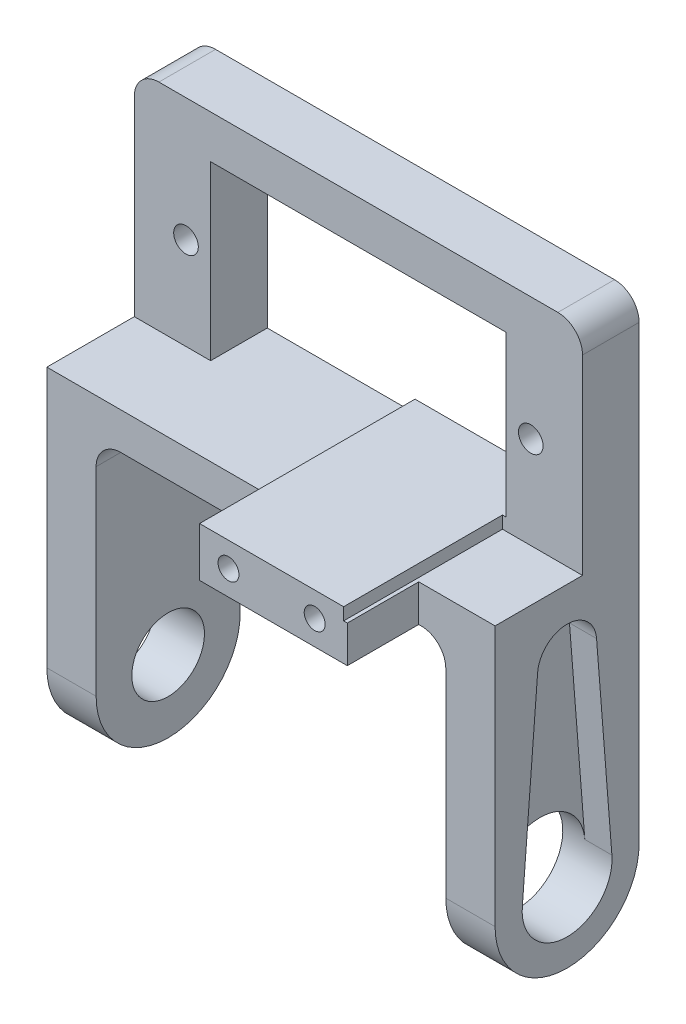
SolidWorks part; units mm, degrees
note: The reader was unsure of these and kept them because the rebuilt part matched: shared geometry of "草图1<3>", "草图1<4>", "草图2<3>", "草图1<6>", "草图4<3>", "草图2<4>", "草图2<5>".
ref_plane "前视基准面" through (0, 0, 0) normal (0, 0, 1) x (1, 0, 0)
ref_plane "上视基准面" through (0, 0, 0) normal (0, 1, 0) x (1, 0, 0)
ref_plane "右视基准面" through (0, 0, 0) normal (1, 0, 0) x (0, 0, -1)
sketch "草图1" plane through (0, 0, 0) normal (0, 0, 1) x (1, 0, 0)
  line L0 (0, 0) -> (0, 44.5)
  line L1 (0, 44.5) -> (36.4, 44.5)
  line L2 (36.4, 44.5) -> (36.4, 0)
  line L3 (36.4, 0) -> (32.4, 0)
  line L4 (32.4, 0) -> (32.4, 24)
  line L5 (32.4, 24) -> (4, 24)
  line L6 (4, 24) -> (4, 0)
  line L7 (4, 0) -> (0, 0)
  line L8 (6.2, 41) -> (6.2, 28)
  line L9 (6.2, 28) -> (30.2, 28)
  line L10 (30.2, 28) -> (30.2, 41)
  line L11 (30.2, 41) -> (6.2, 41)
  line L12 (18.2, 37.1433) -> (18.2, 17.0175) construction
  line L13 (5.5, 34.5) -> (29.5, 34.5) construction
  line L14 (18.2, 28) -> (18.2, 27)
  line L15 (0, 27) -> (35, 27) construction
  line L16 (6.5, 27) -> (6.5, 28) construction
  line L17 (6.5, 27) -> (0, 27) construction
  line L18 (6.5, 27) -> (18.2, 27) construction
  line L19 (12.35, 27) -> (12.35, 38.1786) construction
  line L20 (6.2, 28) -> (6.2, 24)
  line L21 (6.6587, 26) -> (12.3538, 26) construction
  line L22 (18.2, 28) -> (18.2, 24)
  line L23 (29.9, 27) -> (29.9, 28)
  line L24 (29.9, 27) -> (36.4, 27)
  line L25 (30.2, 27) -> (30.2, 24)
  line L26 (0, 27) -> (6.2, 27)
  line L27 (6.2, 27) -> (6.2, 28)
  line L28 (6.2, 27) -> (18.2, 27)
  circle A0 centre (32.2, 34.5) radius 1
  circle A1 centre (4.2, 34.5) radius 1
  circle A2 centre (15.85, 26) radius 0.85 construction
  circle A3 centre (8.85, 26) radius 0.85 construction
  circle A4 centre (27.55, 26) radius 0.85
  circle A5 centre (20.55, 26) radius 0.85
  point P16 (6.2, 34.5)
  point P28 (18.2, 26)
  dimension "D8" = 2
  dimension "D13" = 1.7
  dimension "D1" = 36.4
  dimension "D2" = 4
  dimension "D3" = 24
  dimension "D4" = 13
  dimension "D5" = 3.5
  dimension "D6" = 4
  dimension "D7" = 24
  dimension "D9" = 2
  dimension "D10" = 1
  dimension "D12" = 11.7
  dimension "D14" = 7
extrude "凸台-拉伸1" add sketch "草图1" along normal blind 4.6 contours L20 L8 L11 L10 L9 L14 L15 L2 L1 L0 L17 A1 A0
extrude "凸台-拉伸2" add sketch "草图1<3>" along normal blind 11.7 contours L15 L22 L5 L4 L3 L2 | L20 L17 L0 L7 L6 L5
sketch "草图1<3>" plane through (0, 0, 0) normal (0, 0, 1) x (1, 0, 0) same geometry as "草图1"
extrude "凸台-拉伸3" add sketch "草图1<4>" along normal blind 11.7 contours L22 L14 L9 L16 L17 L20 L5 A3 A2
sketch "草图1<4>" plane through (0, 0, 0) normal (0, 0, 1) x (1, 0, 0) same geometry as "草图1"
sketch "草图2" plane through (0, 0, 0) normal (-1, 0, 0) x (0, 0, 1)
  line L0 (0, 5.85) -> (13.9097, 5.85) construction
  line L1 (8.2426, 21.9881) -> (9.4888, 6.1361)
  line L2 (11.7, 0) -> (0, 0) construction
  line L3 (5.85, 0) -> (5.85, 14.3706) construction
  line L4 (3.4574, 21.9881) -> (2.2112, 6.1361)
  line L5 (11.7, 0) -> (0, 0)
  circle A0 centre (5.85, 5.85) radius 3.65
  arc A1 (8.2426, 21.9881) -> (3.4574, 21.9881) centre (5.85, 21.8) ccw
  point P5 (5.85, 7.1853)
  point P9 (5.85, 0)
  point P16 (5.85, 24.2)
  point P17 (5.85, 2.2)
  dimension "D2" = 7.3
  dimension "D3" = 4.8
  dimension "D1" = 5.85
  dimension "D4" = 22
extrude "切除-拉伸1" cut sketch "草图2" against normal blind 24.5 contours A0
extrude "切除-拉伸2" cut sketch "草图2<3>" against normal blind 2.2 contours L1 A1 L4 A0
sketch "草图2<3>" plane through (0, 0, 0) normal (-1, 0, 0) x (0, 0, 1) same geometry as "草图2"
fillet "圆角2" radius 5.85 1 edges at (2, 0, 0)
fillet "圆角3" radius 5.85 1 edges at (34.4, 0, 0)
fillet "圆角4" radius 5.85 3 edges at (34.4, 0, 11.7) (32.4, 0, 8.775) (36.4, 0, 8.775)
fillet "圆角1" radius 5.85 3 edges at (2, 0, 11.7) (0, 0, 8.775) (4, 0, 8.775)
fillet "圆角5" radius 2 1 edges at (0, 44.5, 2.3)
fillet "圆角6" radius 2 1 edges at (36.4, 44.5, 2.3)
fillet "圆角8" radius 2 1 edges at (4, 24, 5.85)
sketch "草图3" plane through (36.4, 0, 0) normal (1, 0, 0) x (0, 0, -1)
  line L3 (0, 5.85) -> (0, 22)
  line L4 (0, 22) -> (-11.7, 22)
  line L5 (-11.7, 22) -> (-11.7, 5.85)
  line L6 (0, 5.85) -> (0, 22)
  line L7 (0, 22) -> (-11.7, 22)
  line L8 (-11.7, 22) -> (-11.7, 5.85)
  circle A0 centre (-5.85, 5.85) radius 2.95
  arc A2 (-11.7, 5.85) -> (-5.85, 0) centre (-5.85, 5.85) ccw
  arc A3 (-5.85, 0) -> (0, 5.85) centre (-5.85, 5.85) ccw
  arc A4 (-11.7, 5.85) -> (-5.85, 0) centre (-5.85, 5.85) ccw
  arc A5 (-5.85, 0) -> (0, 5.85) centre (-5.85, 5.85) ccw
  dimension "D2" = 5.9
  dimension "D1" = 0
extrude "切除-拉伸3" cut sketch "草图3" against normal blind 10 contours A0
extrude "凸台-拉伸5" add sketch "草图1<6>" along normal blind 17.5 contours L25 L24 L23 L9 L14 L22 L5 A4 A5
sketch "草图1<6>" plane through (0, 0, 0) normal (0, 0, 1) x (1, 0, 0) same geometry as "草图1"
fillet "圆角9" radius 2 1 edges at (32.4, 24, 5.85)
sketch "草图4" plane through (36.4, 0, 0) normal (1, 0, 0) x (0, 0, -1)
  line L2 (-8.2426, 21.9881) -> (-9.4888, 6.1361)
  line L3 (-2.2112, 6.1361) -> (-3.4574, 21.9881)
  line L4 (-8.2426, 21.9881) -> (-9.4888, 6.1361)
  line L5 (-2.2112, 6.1361) -> (-3.4574, 21.9881)
  circle A0 centre (-5.85, 5.85) radius 3.65 construction
  circle A1 centre (-5.85, 5.85) radius 3.65
  arc A2 (-3.4574, 21.9881) -> (-8.2426, 21.9881) centre (-5.85, 21.8) ccw
  arc A3 (-2.2112, 6.1361) -> (-9.4888, 6.1361) centre (-5.85, 5.85) ccw
  arc A4 (-3.4574, 21.9881) -> (-8.2426, 21.9881) centre (-5.85, 21.8) ccw
  arc A5 (-2.2112, 6.1361) -> (-9.4888, 6.1361) centre (-5.85, 5.85) ccw
  circle M5 centre (-5.85, 5.85) radius 2.95
  dimension "D1" = 0
sketch "草图5" plane through (0, 0, 0) normal (-1, 0, 0) x (0, 0, 1)
  circle A0 centre (5.85, 5.85) radius 2.95 construction
  circle A1 centre (5.85, 5.85) radius 2.95
extrude "切除-拉伸4" cut sketch "草图4" against normal blind 2.2 contours L5 A4 L4 A1
extrude "切除-拉伸5" cut sketch "草图4<3>" against normal blind 10.2 contours A1 M5
sketch "草图4<3>" plane through (36.4, 0, 0) normal (1, 0, 0) x (0, 0, -1) same geometry as "草图4"
extrude "凸台-拉伸6" add sketch "草图2<4>" against normal blind 2.2 contours L1 A1 L4 A0
sketch "草图2<4>" plane through (0, 0, 0) normal (-1, 0, 0) x (0, 0, 1) same geometry as "草图2"
extrude "凸台-拉伸7" add sketch "草图2<5>" against normal up to surface (4 mm away) contours A0 up to face at (4, 9.5, 5.85)
sketch "草图2<5>" plane through (0, 0, 0) normal (-1, 0, 0) x (0, 0, 1) same geometry as "草图2"
extrude "切除-拉伸6" cut sketch "草图5" against normal blind 8.2
